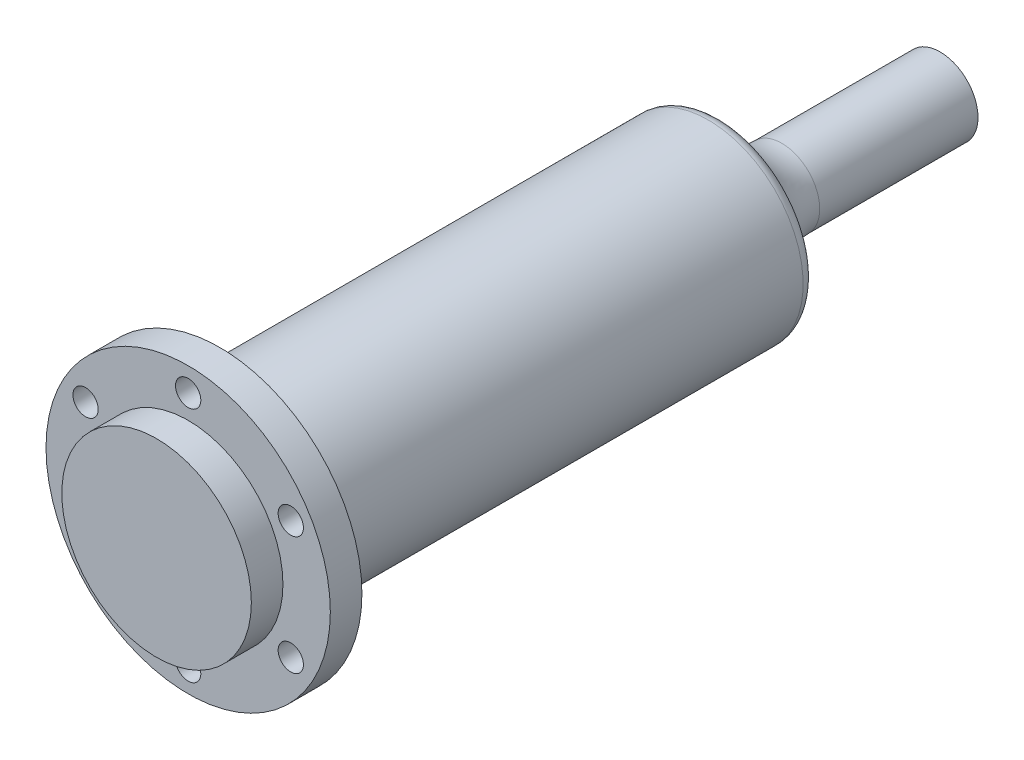
SolidWorks part; units mm, degrees
material "6063-O, Extruded Rod (SS)"
ref_plane "Front Plane" through (0, 0, 0) normal (0, 0, 1) x (1, 0, 0)
ref_plane "Top Plane" through (0, 0, 0) normal (0, 1, 0) x (1, 0, 0)
ref_plane "Right Plane" through (0, 0, 0) normal (1, 0, 0) x (0, 0, -1)
sketch "Sketch1" plane through (0, 0, 0) normal (0, 0, 1) x (1, 0, 0)
  circle A0 centre (0, 0) radius 15
  dimension "D1" = 30
extrude "Boss-Extrude1" add sketch "Sketch1" along normal blind 72
sketch "Sketch3" plane through (0, 0, 72) normal (0, 0, 1) x (1, 0, 0)
  circle A0 centre (0, 0) radius 7.5
  circle A1 centre (0, 0) radius 15
  dimension "D1" = 30
  dimension "D2" = 15
extrude "Boss-Extrude2" add sketch "Sketch3" along normal blind 17
sketch "Sketch4" plane through (0, 0, 89) normal (0, 0, 1) x (1, 0, 0)
  circle A0 centre (0, 0) radius 12.5
  circle A1 centre (0, 0) radius 22.5
  circle A2 centre (0, 0) radius 18.75 construction
  circle A3 centre (0, 18.75) radius 2
  circle A7 centre (16.238, 9.375) radius 2
  circle A8 centre (16.238, -9.375) radius 2
  circle A9 centre (0, -18.75) radius 2
  circle A10 centre (-16.238, -9.375) radius 2
  circle A11 centre (-16.238, 9.375) radius 2
  point P16 (0, 0)
  point P20 (0, 0)
  dimension "D1" = 25
  dimension "D2" = 45
  dimension "D3" = 37.5
  dimension "D4" = 4
  dimension "D5" = 6
extrude "Boss-Extrude3" add sketch "Sketch4" against normal blind 5 from offset 5 offset against normal yes
sketch "Sketch6" plane through (0, 0, 0) normal (0, 0, -1) x (-1, 0, 0)
  circle A0 centre (0, 0) radius 6
  circle A1 centre (0, 0) radius 3
  dimension "D1" = 6
  dimension "D2" = 12
extrude "Boss-Extrude4" add sketch "Sketch6" along normal blind 35
sketch "Sketch7" plane through (0, 0, -35) normal (0, 0, -1) x (-1, 0, 0)
  line L0 (0, 0) -> (0, 6) construction
  circle A0 centre (0, 0) radius 6 construction
  circle A1 centre (0, 0) radius 6 construction
ref_plane "Plane1" through (0, 6, -35) normal (0, 1, 0) x (1, 0, 0)
sketch "Sketch9" plane through (0, 0, 72) normal (0, 0, 1) x (1, 0, 0)
  circle A0 centre (0, 0) radius 7.5
  dimension "D1" = 15
extrude "Cut-Extrude2" cut sketch "Sketch9" against normal offset from surface (67 mm away) 5 up to face at (-3, 0, 0)
sketch "Sketch10" plane through (0, 0, 0) normal (0, 0, -1) x (-1, 0, 0)
  circle A0 centre (0, 0) radius 3
  dimension "D1" = 6
sketch "Sketch12" plane through (0, 0, 89) normal (0, 0, 1) x (1, 0, 0)
  circle A0 centre (0, 0) radius 7.5
extrude "Cut-Extrude3" cut sketch "Sketch10" against normal up to surface (5 mm away) up to face at (7.5, 0, 5)
sketch "Sketch11" plane through (0, 0, 89) normal (0, 0, 1) x (1, 0, 0)
  circle A0 centre (0, 0) radius 7.5
fillet "Fillet1" radius 10 1 edges at (6, 0, 0)
fillet "Fillet2" radius 2 1 edges at (15, 0, 0)
extrude "Boss-Extrude5" add sketch "Sketch12" against normal up to surface (84 mm away) contours A0 up to face at (3, 0, 5)
